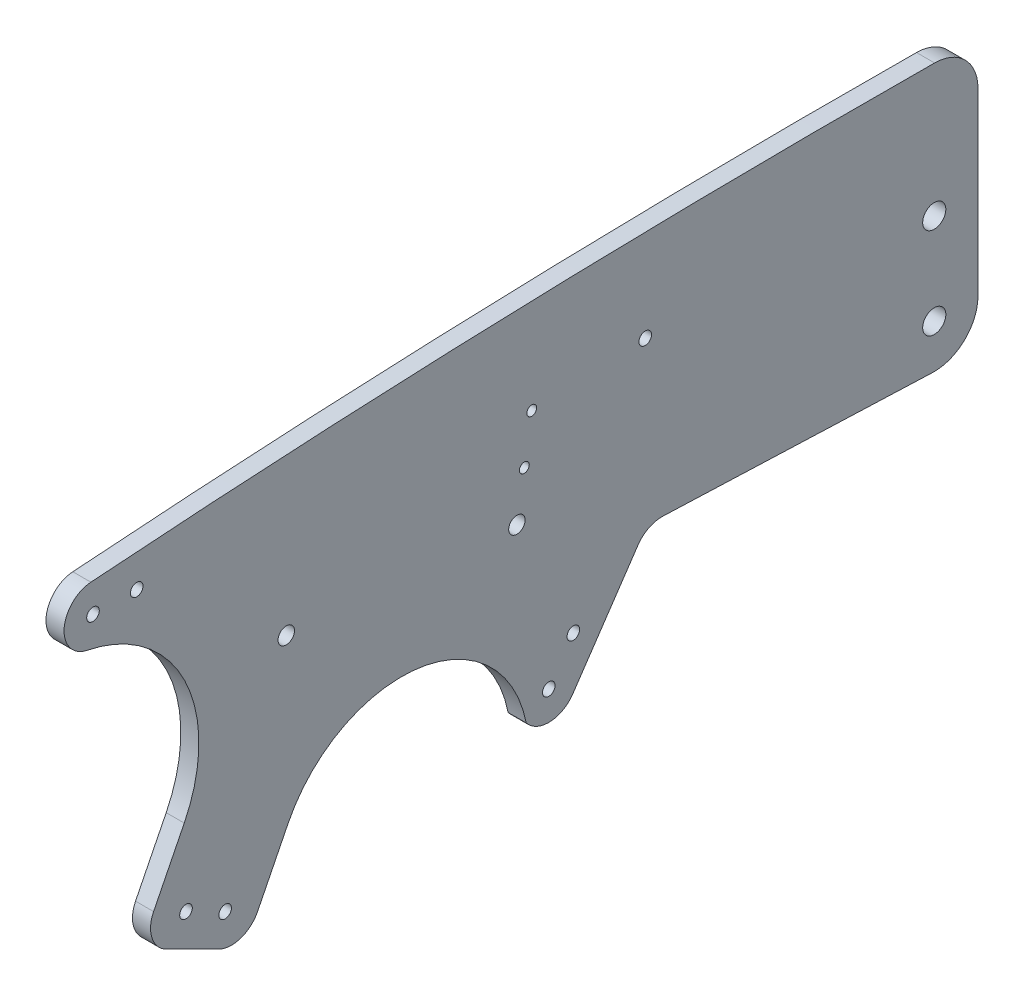
SolidWorks part; units mm, degrees
material "Beech"
ref_plane "Front" through (0, 0, 0) normal (0, 0, 1) x (1, 0, 0)
ref_plane "Top" through (0, 0, 0) normal (0, 1, 0) x (1, 0, 0)
ref_plane "Right" through (0, 0, 0) normal (1, 0, 0) x (0, 0, -1)
ref_axis "side-side" through (80.9, 0, 0) along (-1, 0, 0)
ref_axis "up-down" through (0, 50, 0) along (0, -1, 0)
ref_axis "front-back" through (0, 0, -80.9) along (0, 0, 1)
sketch "Sketch1" plane through (0, 0, 0) normal (1, 0, 0) x (0, 0, -1)
  line L10 (-364.4589, -24.3751) -> (-23.6778, -37.6187)
  line L15 (-535.345, -46.1379) -> (-441.6488, -92.9736)
  line L16 (-391.2831, -61.8422) -> (-391.2831, -41.4241)
  line L20 (-30.1249, 32.6847) -> (-392.4, 46.7636)
  line L151 (-405.9448, 45.5629) -> (-527.2317, 18.9913)
  circle A2 centre (0, 0) radius 11.5
  arc A12 (-527.2317, 18.9913) -> (-535.345, -46.1379) centre (-519.7834, -15.0065) ccw
  arc A13 (-441.6488, -92.9736) -> (-391.2831, -61.8422) centre (-426.0872, -61.8422) ccw
  arc A15 (-23.6778, -37.6187) -> (-30.1249, 32.6847) centre (0, 0) ccw
  arc A23 (-391.2831, -41.4241) -> (-364.4589, -24.3751) centre (-394.4803, -6.7672) ccw
  arc A268 (-392.4, 46.7636) -> (-405.9448, 45.5629) centre (-394.4803, -6.7672) ccw
sketch "Sketch3" plane through (0, 0, 0) normal (1, 0, 0) x (0, 0, -1)
  circle A2 centre (-426.0872, -61.8422) radius 2.3813
  circle A4 centre (-394.4803, -6.7672) radius 2.3813
  circle A6 centre (-457.7546, -1.4172) radius 2.3813
  circle A8 centre (-519.7834, -15.0065) radius 2.3812
  circle A92 centre (-474.5189, -58.6553) radius 1.7272
  circle A93 centre (-485.2525, -53.2899) radius 1.7272
  circle A94 centre (-385.7372, -50.1857) radius 1.7272
  circle A95 centre (-379.0063, -40.2511) radius 1.7272
  circle A96 centre (-498.7714, 29.9682) radius 1.7272
  circle A97 centre (-510.7706, 30.1019) radius 1.7272
  circle A98 centre (-359.2766, 19.9282) radius 1.7272
  circle A99 centre (-367.6668, 28.5075) radius 1.7272
sketch "Sketch4" plane through (0, 0, 0) normal (1, 0, 0) x (0, 0, -1)
  line L12 (-460.0851, -49.3735) -> (-460.8018, -59.3478)
  line L13 (-498.5693, -42.5979) -> (-463.7881, -45.0971)
  line L14 (-516.1804, 35.9104) -> (-543.504, 10.4623)
  line L15 (-367.5783, 36.4445) -> (-510.6822, 38.0389)
  line L16 (-371.1745, -41.5427) -> (-359.8351, 27.2159)
  line L17 (-397.2737, -81.3642) -> (-372.435, -44.7034)
  circle A1 centre (-367.6668, 28.5075) radius 1.905
  circle A3 centre (-510.7706, 30.1019) radius 1.905
  circle A5 centre (-379.0063, -40.2511) radius 1.905
  arc A12 (-460.8018, -59.3478) -> (-397.2737, -81.3642) centre (-426.0872, -61.8422) ccw
  arc A13 (-460.0851, -49.3735) -> (-463.7881, -45.0971) centre (-464.0748, -49.0868) ccw
  arc A14 (-543.504, 10.4623) -> (-498.5693, -42.5979) centre (-519.7834, -15.0065) ccw
  arc A15 (-510.6822, 38.0389) -> (-516.1804, 35.9104) centre (-510.7706, 30.1019) ccw
  arc A16 (-359.8351, 27.2159) -> (-367.5783, 36.4445) centre (-367.6668, 28.5075) ccw
  arc A17 (-372.435, -44.7034) -> (-371.1745, -41.5427) centre (-379.0063, -40.2511) ccw
sketch "Sketch2" plane through (0, 0, 0) normal (1, 0, 0) x (0, 0, -1)
  line L0 (-268, 33.638) -> (-268, -15.6483)
  line L1 (-354.3699, -24.7672) -> (-280.466, -27.6393)
  line L3 (-397.2737, -81.3642) -> (-372.435, -44.7034) construction
  line L4 (0, 50) -> (0, -50) construction
  line L5 (-364.4589, -24.3751) -> (-23.6778, -37.6187) construction
  line L7 (-30.1249, 32.6847) -> (-503.0574, 37.954) construction
  line L16 (-379.1659, -54.6379) -> (-361.3036, -28.2739)
  line L17 (-354.3699, -24.7672) -> (-23.6778, -37.6187) construction
  line L20 (-485.7375, -32.025) -> (-494.1451, -48.8447)
  line L22 (-490.5663, -59.5775) -> (-476.359, -66.6793)
  line L23 (-535.345, -46.1379) -> (-441.6488, -92.9736) construction
  line L24 (-465.6263, -63.1004) -> (-457.2186, -46.2806)
  circle A0 centre (-379.0063, -40.2511) radius 1.7272 construction
  arc A1 (-23.6778, -37.6187) -> (-30.1249, 32.6847) centre (0, 0) ccw construction
  circle A2 centre (-379.0063, -40.2511) radius 1.7272
  arc A6 (-23.6778, -37.6187) -> (-30.1249, 32.6847) centre (0, 0) ccw construction
  circle A10 centre (0, 0) radius 11.5 construction
  circle A11 centre (0, 0) radius 11.5 construction
  arc A13 (-391.9332, -55.1469) -> (-457.2186, -46.2806) centre (-426.0872, -61.8422) ccw
  arc A14 (-441.6488, -92.9736) -> (-391.2831, -61.8422) centre (-426.0872, -61.8422) ccw construction
  circle A15 centre (-367.6668, 28.5075) radius 1.7272 construction
  circle A17 centre (-510.7706, 30.1019) radius 1.7272
  arc A19 (-510.6822, 38.0389) -> (-516.1804, 35.9104) centre (-510.7706, 30.1019) ccw construction
  arc A20 (-511.3546, 38.0179) -> (-512.3258, 22.3183) centre (-510.7706, 30.1019) ccw
  circle A24 centre (-359.2766, 19.9282) radius 1.7272 construction
  circle A25 centre (-457.7546, -1.4172) radius 2.2542
  circle A26 centre (-394.4803, -6.7672) radius 2.2542
  arc A28 (-362.7596, 34.7464) -> (-362.755, 34.7428) centre (-367.6668, 28.5075) ccw construction
  arc A29 (-391.9332, -55.1469) -> (-379.1659, -54.6379) centre (-385.7372, -50.1857) ccw
  arc A30 (-485.7375, -32.025) -> (-512.3258, 22.3183) centre (-519.7834, -15.0065) ccw
  arc A31 (-543.504, 10.4623) -> (-498.5693, -42.5979) centre (-519.7834, -15.0065) ccw construction
  circle A33 centre (-367.6668, 28.5075) radius 1.7272 construction
  circle A34 centre (-359.2766, 19.9282) radius 1.7272
  circle A35 centre (-385.7372, -50.1857) radius 1.7272
  arc A36 (-448.0381, -34.8332) -> (-483.1223, -25.2398) centre (-457.7546, -1.4172) cw construction
  arc A37 (-354.3699, -24.7672) -> (-361.3036, -28.2739) centre (-354.6806, -32.7612) ccw
  circle A38 centre (-457.7546, -1.4172) radius 2.3813 construction
  circle A39 centre (-394.4803, -6.7672) radius 2.3813 construction
  circle A40 centre (-510.7706, 30.1019) radius 1.7272 construction
  circle A41 centre (-498.7714, 29.9682) radius 1.7272 construction
  circle A42 centre (-390.4197, 18.3061) radius 1.3526
  circle A43 centre (-392.45, 5.7695) radius 1.3526
  arc A44 (-476.359, -66.6793) -> (-465.6263, -63.1004) centre (-472.7821, -59.5235) ccw
  arc A45 (-494.1451, -48.8447) -> (-490.5663, -59.5775) centre (-486.9894, -52.4217) ccw
  circle A46 centre (-385.7372, -50.1857) radius 1.7272 construction
  circle A47 centre (-498.7714, 29.9682) radius 1.7272
  circle A48 centre (-474.5189, -58.6553) radius 1.7272 construction
  circle A49 centre (-485.2525, -53.2899) radius 1.7272 construction
  circle A50 centre (-474.5189, -58.6553) radius 1.7272
  circle A51 centre (-485.2525, -53.2899) radius 1.7272
  arc A52 (-30.1249, 32.6847) -> (-511.3546, 38.0179) centre (-302.1394, -2797.9349) ccw construction
  circle A53 centre (-280, -15.6483) radius 3.175
  circle A54 centre (-390.4197, 18.3061) radius 1.3526 construction
  circle A55 centre (-392.45, 5.7695) radius 1.3526 construction
  arc A56 (-511.3546, 38.0179) -> (-279.9062, 45.6377) centre (-302.1394, -2797.9349) cw
  arc A57 (-268, -15.6483) -> (-280.466, -27.6393) centre (-280, -15.6483) cw
  arc A58 (-268, 33.638) -> (-279.9062, 45.6377) centre (-280, 33.638) ccw
  circle A59 centre (-280, 9.3517) radius 3.175
  point P100 (0, 0)
  point P101 (0, 0)
  dimension "D1" = 34.8
  dimension "D2" = 8
  dimension "D3" = 4.5085
  dimension "D4" = 8
  dimension "D5" = 8
  dimension "D6" = 15.875
  dimension "D7" = 61.0608
  dimension "D8" = 12
  dimension "D10" = 12
  dimension "D11" = 12
  dimension "D12" = 280
  dimension "D13" = 6.35
  dimension "D14" = 25
  dimension "D9" = 70
extrude "Boss-Extrude1" add sketch "Sketch2" along normal blind 4.953
